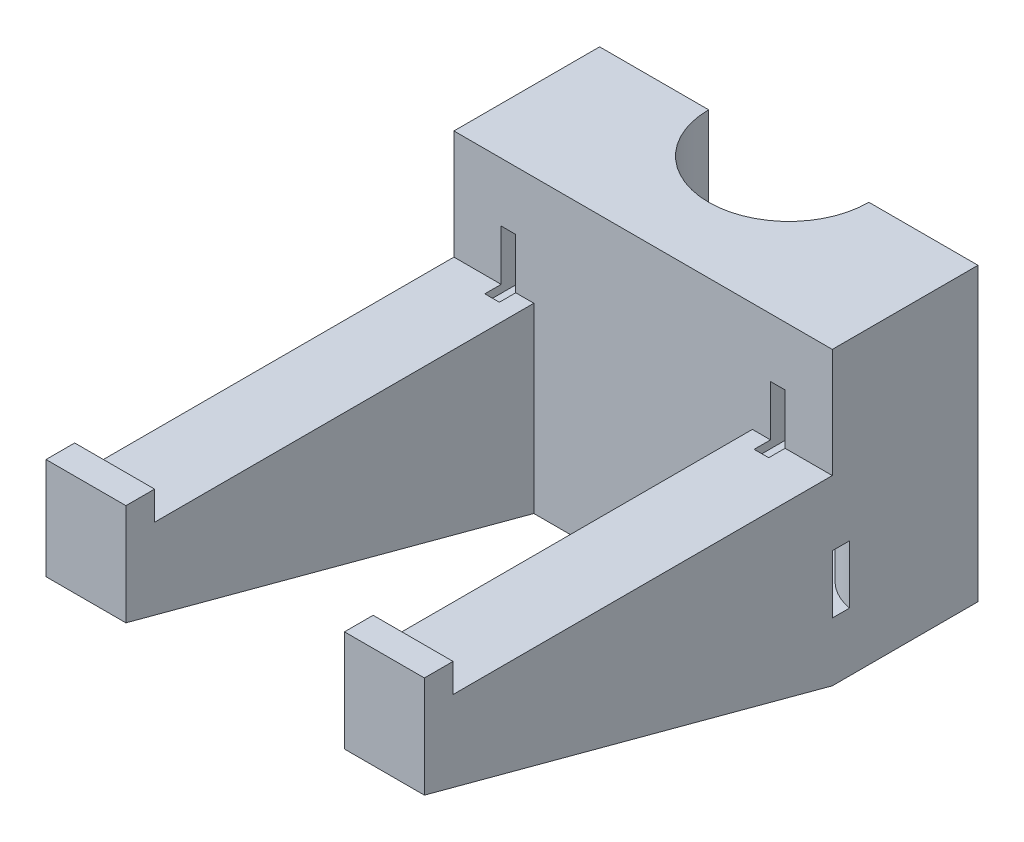
SolidWorks part; units mm, degrees
ref_plane "Front Plane" through (0, 0, 0) normal (0, 0, 1) x (1, 0, 0)
ref_plane "Top Plane" through (0, 0, 0) normal (0, 1, 0) x (1, 0, 0)
ref_plane "Right Plane" through (0, 0, 0) normal (1, 0, 0) x (0, 0, -1)
sketch "Sketch1" plane through (0, 0, 0) normal (0, 1, 0) x (1, 0, 0)
  line L0 (-13.97, 0) -> (13.97, 0)
  line L1 (-13.9342, 1) -> (13.9342, 1)
  line L2 (-32.9842, -25.4) -> (-32.9842, -96.52)
  line L3 (-32.9842, 0) -> (32.9842, 0)
  line L4 (-32.9842, 0) -> (-32.9842, -25.4)
  line L5 (-32.9842, -25.4) -> (32.9842, -25.4)
  line L6 (32.9842, 0) -> (32.9842, -25.4)
  line L7 (-32.9842, 1) -> (32.9842, 1)
  line L8 (-32.9842, 1) -> (-32.9842, 20.05)
  line L9 (-32.9842, 20.05) -> (32.9842, 20.05)
  line L10 (32.9842, 1) -> (32.9842, 20.05)
  line L11 (-19.05, -25.4) -> (19.05, -25.4)
  line L12 (-19.05, -25.4) -> (-19.05, -96.52)
  line L13 (-19.05, -96.52) -> (19.05, -96.52)
  line L14 (19.05, -25.4) -> (19.05, -96.52)
  line L15 (-32.9842, -96.52) -> (-19.05, -96.52)
  line L16 (19.05, -96.52) -> (32.9842, -96.52)
  line L17 (32.9842, -96.52) -> (32.9842, -25.4)
  circle A0 centre (0, 0) radius 13.97
  point P19 (-19.05, -67.0873)
  dimension "D1" = 27.94
  dimension "D2" = 1
  dimension "D3" = 19.05
  dimension "D4" = 19.05
  dimension "D5" = 19.05
  dimension "D6" = 38.1
  dimension "D7" = 13.9342
  dimension "D8" = 65.9683
  dimension "D9" = 25.4
  dimension "D10" = 71.12
extrude "Boss-Extrude1" add sketch "Sketch1" along normal blind 50.8 contours A0 L3 L4 L5 L6 region at (0, 0, 14.2162)
extrude "Boss-Extrude2" add sketch "Sketch1<4>" along normal up to surface (50.8 mm away) contours L2 L15 L12 L5 | L16 L17 L5 L14 region at (-26.0171, 0, 60.96) region at (26.0171, 0, 60.96) up to face at (0, 50.8, 10.795)
sketch "Sketch1<4>" plane through (0, 0, 0) normal (0, 1, 0) x (1, 0, 0) same geometry as "Sketch1"
sketch "Sketch2" plane through (0, 0, 0) normal (1, 0, 0) x (0, 0, -1)
  line L0 (-25.4, 50.8) -> (-25.4, 0)
  line L1 (0, 50.8) -> (-96.52, 50.8) construction
  line L2 (0, 0) -> (-96.52, 0) construction
  line L3 (0, 50.8) -> (0, 0) construction
  line L4 (-96.52, 19.05) -> (-25.4, 19.05)
  line L5 (-96.52, 50.8) -> (-96.52, 0) construction
  line L6 (-96.52, 19.05) -> (-96.52, 0)
  line L7 (-96.52, 0) -> (-25.4, 0)
  line L8 (-96.52, 50.8) -> (-96.52, 31.75)
  line L9 (-96.52, 31.75) -> (-25.4, 31.75)
  line L10 (-25.4, 50.8) -> (-96.52, 50.8)
  line L11 (-96.52, 19.05) -> (-25.4, 0)
  line L12 (-96.52, 36.75) -> (-91.52, 36.75)
  line L13 (-91.52, 36.75) -> (-91.52, 31.75)
  line L15 (-25.4, 20.4) -> (-22.4, 20.4)
  line L16 (-25.4, 20.4) -> (-25.4, 10.24)
  line L17 (-25.4, 10.24) -> (-22.4, 10.24)
  line L18 (-22.4, 20.4) -> (-22.4, 10.24)
  dimension "D4" = 19.05
  dimension "D1" = 25.4
  dimension "D2" = 12.7
  dimension "D5" = 5
  dimension "D6" = 66.12
  dimension "D7" = 5
  dimension "D3" = 10.24
  dimension "D8" = 20.4
  dimension "D9" = 3
extrude "Cut-Extrude1" cut sketch "Sketch2" against normal through all both and the other way through all contours L0 L10 L8 L9 | L11 L4 L6 L7 region at (0, 41.4071, 60.3385) region at (0, 6.35, 72.8133)
sketch "Sketch3" plane through (0, 0, 0) normal (0, 0, 1) x (1, 0, 0)
  line L0 (32.9842, 50.8) -> (32.9842, 0) construction
  line L1 (-32.9842, 50.8) -> (-32.9842, 0) construction
  line L2 (-32.9842, 0) -> (-13.97, 0) construction
  line L3 (0, 50.8) -> (0, 0) construction
  line L4 (24.7492, 40.56) -> (22.2092, 40.56)
  line L5 (24.7492, 40.56) -> (24.7492, 30.4)
  line L6 (24.7492, 30.4) -> (22.2092, 30.4)
  line L7 (22.2092, 40.56) -> (22.2092, 30.4)
  line L8 (13.97, 50.8) -> (-13.97, 50.8) construction
  line L9 (-24.7492, 30.4) -> (-22.2092, 30.4)
  line L10 (-22.2092, 40.56) -> (-22.2092, 30.4)
  line L11 (-24.7492, 40.56) -> (-22.2092, 40.56)
  line L12 (-24.7492, 40.56) -> (-24.7492, 30.4)
  line L13 (23.4792, 25.4) -> (-23.4792, 25.4) construction
  line L14 (-24.7492, 10.24) -> (-24.7492, 20.4)
  line L15 (-24.7492, 10.24) -> (-22.2092, 10.24)
  line L16 (-22.2092, 10.24) -> (-22.2092, 20.4)
  line L17 (-24.7492, 20.4) -> (-22.2092, 20.4)
  line L18 (24.7492, 20.4) -> (22.2092, 20.4)
  line L19 (22.2092, 10.24) -> (22.2092, 20.4)
  line L20 (24.7492, 10.24) -> (22.2092, 10.24)
  line L21 (24.7492, 10.24) -> (24.7492, 20.4)
  circle A0 centre (23.4792, 25.4) radius 3.937
  circle A1 centre (-23.4792, 25.4) radius 3.937
  point P16 (23.4792, 40.56)
  dimension "D7" = 5
  dimension "D1" = 7.874
  dimension "D2" = 9.505
  dimension "D3" = 9.505
  dimension "D4" = 25.4
  dimension "D5" = 10.16
  dimension "D6" = 2.54
extrude "Cut-Extrude2" cut sketch "Sketch3" along normal blind 8.255
extrude "Cut-Extrude3" cut sketch "Sketch3<2>" along normal blind 28.255 contours L4 L7 L6 L5 | L11 L12 L9 L10 | L20 L21 L18 L19 | L17 L14 L15 L16 region at (23.4792, 35.48, 0) region at (-23.4792, 35.48, 0) region at (-23.4792, 15.32, 0) region at (23.4792, 15.32, 0)
sketch "Sketch3<2>" plane through (0, 0, 0) normal (0, 0, 1) x (1, 0, 0) same geometry as "Sketch3"
extrude "Cut-Extrude4" cut sketch "Sketch2<4>" against normal up to surface (-22.2092 mm away) from surface contours L18 L15 L0 L17 region at (0, 15.32, 23.9) up to face at (22.2092, 15.32, 14.1275) starting at face at (32.9842, 28.6278, 50.2533)
sketch "Sketch2<4>" plane through (0, 0, 0) normal (1, 0, 0) x (0, 0, -1) same geometry as "Sketch2"
extrude "Cut-Extrude5" cut sketch "Sketch2<5>" against normal up to surface (32.9842 mm away) from surface contours L18 L15 L0 L17 region at (0, 15.32, 23.9) up to face at (-32.9842, 28.6278, 50.2533) starting at face at (-22.2092, 15.32, 14.1275)
sketch "Sketch2<5>" plane through (0, 0, 0) normal (1, 0, 0) x (0, 0, -1) same geometry as "Sketch2"
fillet "Fillet1" radius 10 4 edges at (-24.7492, 15.32, 22.4) (24.7492, 15.32, 22.4) (22.2092, 15.32, 28.255) (-22.2092, 15.32, 28.255)
equation "\"D4@Sketch1\"=\"D3@Sketch1\""
equation "\"D7@Sketch1\"=(\"D8@Sketch1\"-\"D6@Sketch1\")/2"
equation "\"D4@Sketch2\"=(2in-0.5in)/2"
equation "\"D3@Sketch3\"=\"D2@Sketch3\""
